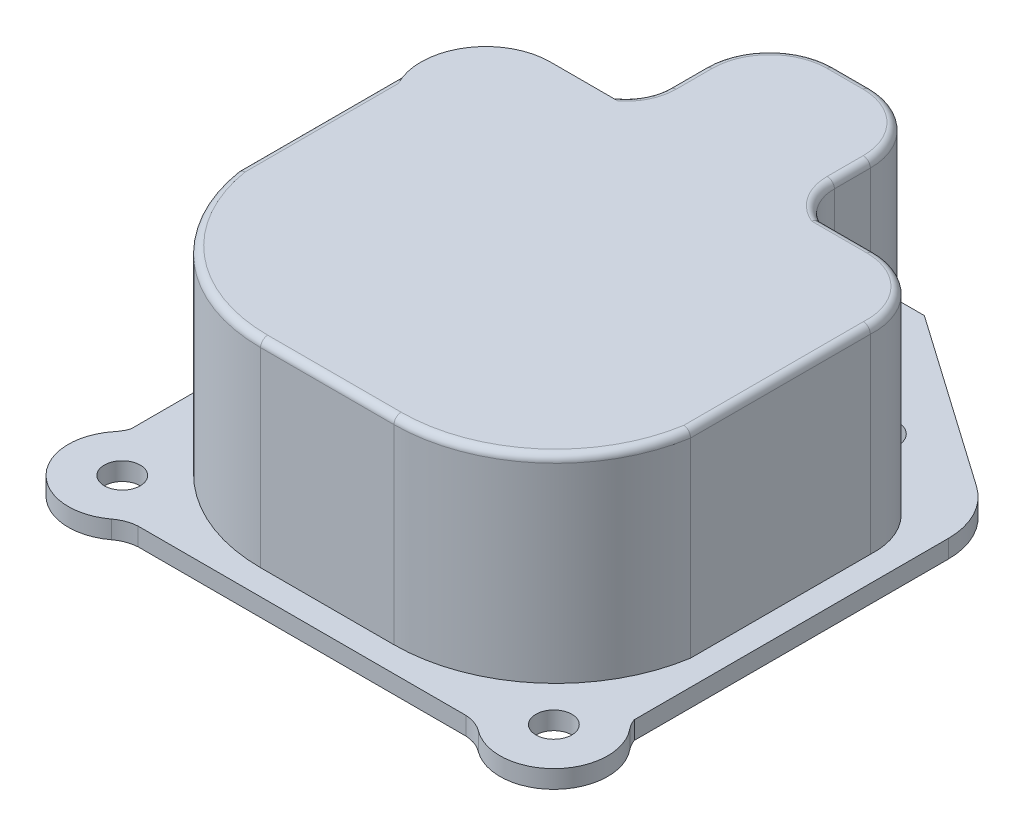
SolidWorks part; units mm, degrees
ref_plane "Front Plane" through (0, 0, 0) normal (0, 0, 1) x (1, 0, 0)
ref_plane "Top Plane" through (0, 0, 0) normal (0, 1, 0) x (1, 0, 0)
ref_plane "Right Plane" through (0, 0, 0) normal (1, 0, 0) x (0, 0, -1)
sketch "Sketch1" plane through (0, 0, 0) normal (0, 1, 0) x (1, 0, 0)
  line L0 (0, 91.5314) -> (0, -91.5314)
  line L1 (-136.0707, 0) -> (136.0707, 0)
  line L2 (-18.5478, -63) -> (18.5478, -63)
  line L3 (63, -25) -> (63, 25)
  line L4 (45.0322, 44.0766) -> (30.0322, 44.0766)
  line L5 (23, 55) -> (23, 65)
  line L6 (5, 83) -> (-5, 83)
  line L7 (-13.0164, 90) -> (13.0164, 90)
  line L8 (13.0164, 90) -> (61.4715, 56.0714)
  line L9 (70, 39.6883) -> (70, -47.6393)
  line L10 (45.5709, -70) -> (-45.5709, -70)
  line L11 (-70, 39.6883) -> (-70, -47.6393)
  line L12 (-13.0164, 90) -> (-61.4715, 56.0714)
  line L13 (-23, 55) -> (-23, 65)
  line L14 (-45.0322, 44.0766) -> (-30.0322, 44.0766)
  line L15 (-63, -25) -> (-63, 25)
  arc A0 (18.5478, -63) -> (63, -25) centre (18.5478, -18) ccw
  arc A1 (63, 25) -> (45.0322, 44.0766) centre (45.0322, 26.0766) ccw
  arc A2 (30.0322, 44.0766) -> (23, 55) centre (35, 55) cw
  arc A3 (23, 65) -> (5, 83) centre (5, 65) ccw
  arc A4 (61.4715, 56.0714) -> (70, 39.6883) centre (50, 39.6883) cw
  arc A5 (50.9859, -71.9894) -> (71.6416, -50.541) centre (60, -60) ccw
  circle A6 centre (60, -60) radius 5
  circle A7 centre (35, 55) radius 5.6564
  arc A8 (50.9859, -71.9894) -> (45.5709, -70) centre (44.9765, -79.9823) ccw
  arc A9 (71.6416, -50.541) -> (70, -47.6393) centre (79.4027, -44.235) cw
  arc A10 (-71.6416, -50.541) -> (-70, -47.6393) centre (-79.4027, -44.235) ccw
  arc A11 (-50.9859, -71.9894) -> (-45.5709, -70) centre (-44.9765, -79.9823) cw
  circle A12 centre (-35, 55) radius 5.6564
  circle A13 centre (-60, -60) radius 5
  arc A14 (-50.9859, -71.9894) -> (-71.6416, -50.541) centre (-60, -60) cw
  arc A15 (-61.4715, 56.0714) -> (-70, 39.6883) centre (-50, 39.6883) ccw
  arc A16 (-23, 65) -> (-5, 83) centre (-5, 65) cw
  arc A17 (-30.0322, 44.0766) -> (-23, 55) centre (-35, 55) ccw
  arc A18 (-63, 25) -> (-45.0322, 44.0766) centre (-45.0322, 26.0766) cw
  arc A19 (-18.5478, -63) -> (-63, -25) centre (-18.5478, -18) cw
  point P0 (-149.9626, 99.1285)
  point P4 (0, 0)
  point P5 (0, 83)
  point P8 (0, 0)
  point P20 (0, -63)
  point P26 (-277.778, -13.357)
  point P34 (71.8049, -52.5906)
  point P35 (0, 0)
  point P39 (-284.4075, 12.0315)
  point P40 (7.0221, 74.597)
  point P41 (-135.8833, 60.3388)
  point P66 (0, -70)
  point P67 (0, 90)
  dimension "D10" = 20
  dimension "D11" = 18
  dimension "D12" = 12
  dimension "D16" = 45
  dimension "D19" = 18
  dimension "D21" = 10
  dimension "D23" = 15
  dimension "D24" = 10
  dimension "D25" = 15
  dimension "D1" = 70
  dimension "D2" = 70
  dimension "D3" = 63
  dimension "D4" = 55
  dimension "D5" = 60
  dimension "D6" = 10
  dimension "D7" = 25
  dimension "D8" = 35
  dimension "D9" = 87.3277
  dimension "D14" = 50
  dimension "D15" = 25
  dimension "D17" = 7
  dimension "D18" = 10
  dimension "D20" = 55
  dimension "D22" = 5
  dimension "D26" = 60
  dimension "D27" = 35
extrude "Boss-Extrude1" add sketch "Sketch1" along normal blind 60 contours A18 L15 L1 L0 L6 A16 L13 A17 L14 | L5 A3 L6 L0 L1 L3 A1 L4 A2 | L2 A0 L3 L1 L0 | A19 L2 L0 L1 L15 region at (26.1361, 0, -31.1739) region at (-26.1361, 0, -31.1739) region at (29.0097, 0, 28.9494) region at (-29.0097, 0, 28.9494)
extrude "Boss-Extrude2" add sketch "Sketch1<3>" along normal blind 5 contours L10 A11 A14 A10 L11 A15 L12 L7 L8 A4 L9 A9 A5 A8
sketch "Sketch1<3>" plane through (0, 0, 0) normal (0, 1, 0) x (1, 0, 0) same geometry as "Sketch1"
extrude "Cut-Extrude4" cut sketch "Sketch1<5>" along normal blind 5 and the other way through all contours A7 | A6 | A13 | A12
sketch "Sketch1<5>" plane through (0, 0, 0) normal (0, 1, 0) x (1, 0, 0) same geometry as "Sketch1"
fillet "Fillet10" radius 2 12 edges at (24.9101, 60, -48.5044) (23, 60, -60) (-24.9101, 60, -48.5044) (-23, 60, -60) (-17.7279, 60, -77.7279) (0, 60, -83) (-47.7882, 60, 52.2053) (0, 60, 63) (-63, 60, 0) (17.7279, 60, -77.7279) (47.7882, 60, 52.2053) (63, 60, 0)
fillet "Fillet11" radius 2 2 edges at (35.6378, 60, -44.0766) (60.4197, 60, -35.416)
